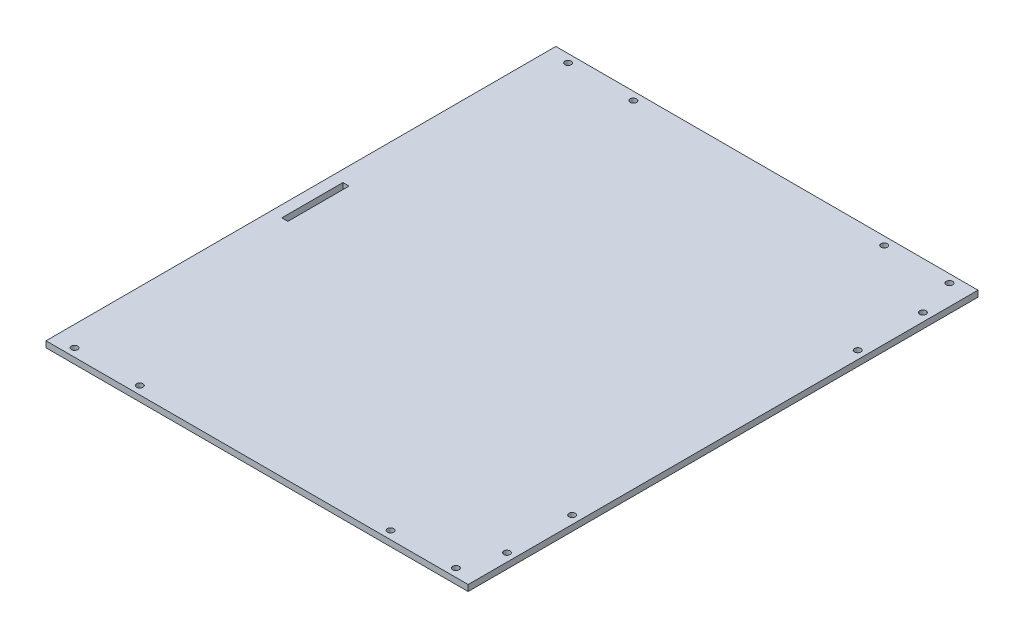
SolidWorks part; units mm, degrees
ref_plane "Front Plane" through (0, 0, 0) normal (0, 0, 1) x (1, 0, 0)
ref_plane "Top Plane" through (0, 0, 0) normal (0, 1, 0) x (1, 0, 0)
ref_plane "Right Plane" through (0, 0, 0) normal (1, 0, 0) x (0, 0, -1)
sketch "Sketch1" plane through (0, 0, 0) normal (0, 1, 0) x (1, 0, 0)
  line L0 (0, 125) -> (207, 125) construction
  line L1 (0, 0) -> (207, 0)
  line L2 (0, 0) -> (0, 250)
  line L3 (0, 250) -> (207, 250)
  line L4 (207, 0) -> (207, 250)
  line L5 (103.5, 250) -> (103.5, 0) construction
  line L6 (7.1, 140) -> (7.1, 110) construction
  line L7 (5.6, 140) -> (8.6, 140)
  line L8 (5.6, 140) -> (5.6, 110)
  line L9 (5.6, 110) -> (8.6, 110)
  line L10 (8.6, 140) -> (8.6, 110)
  circle A0 centre (10, 4) radius 1.55
  circle A4 centre (42, 4) radius 1.55
  circle A5 centre (42, 246) radius 1.55
  circle A6 centre (10, 246) radius 1.55
  circle A7 centre (165, 4) radius 1.55
  circle A8 centre (197, 4) radius 1.55
  circle A9 centre (165, 246) radius 1.55
  circle A10 centre (197, 246) radius 1.55
  circle A11 centre (203, 23) radius 1.55
  circle A12 centre (203, 55) radius 1.55
  circle A13 centre (203, 227) radius 1.55
  circle A14 centre (203, 195) radius 1.55
  point P39 (7.1, 125)
  dimension "D3" = 3.1
  dimension "D8" = 3.1
  dimension "D1" = 250
  dimension "D2" = 207
  dimension "D4" = 4
  dimension "D5" = 10
  dimension "D6" = 32
  dimension "D7" = 23
  dimension "D9" = 4
  dimension "D10" = 32
  dimension "D11" = 7.1
  dimension "D12" = 3
  dimension "D13" = 30
extrude "Boss-Extrude1" add sketch "Sketch1" along normal blind 3
equation "\"cf_tube_outer_diameter\"= 25mm"
equation "\"cf_tube_inner_diameter\"= 21mm"
equation "\"mid_plate_mid_to_top\"= 100mm"
equation "\"mid_plate_mid_to_bottom\"= 30mm"
equation "\"mid_plate_horizontal_spacing\"= 250mm"
equation "\"cf_plate_thickness\"= 3mm"
equation "\"mid_tube_length\"= 500mm"
equation "\"mid_plate_bottom_width\"= 180mm"
equation "\"D1@Sketch1\"=\"mid_plate_horizontal_spacing\""
equation "\"mid_support_plate_distance\"= 250mm"
equation "\"D1@Boss-Extrude1\"=\"cf_plate_thickness\""
equation "\"nut_strip_2_hole_distance\"= 7mm"
equation "\"nut_strip_hole_diameter\"= 2.5mm"
equation "\"nut_strip_hole_to_edge_distance\"= 2.5mm"
equation "\"M3_screw_hole_diameter\"= 3.1mm"
equation "\"D3@Sketch1\"=\"M3_screw_hole_diameter\""
equation "\"D8@Sketch1\"=\"M3_screw_hole_diameter\""
